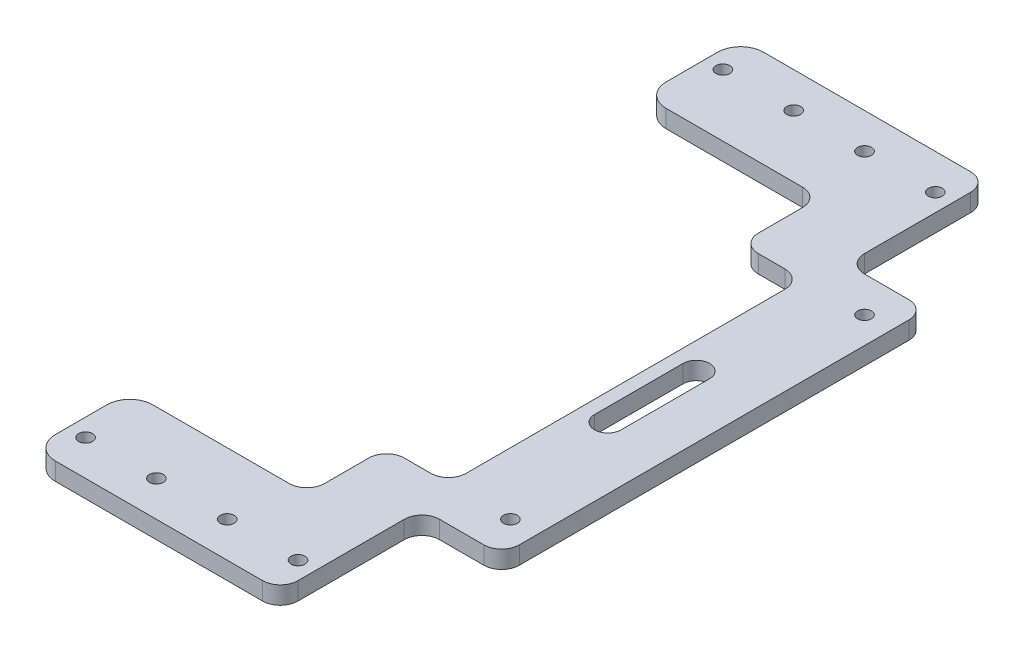
SolidWorks part; units mm, degrees
material "PC High Viscosity"
ref_plane "Front Plane" through (0, 0, 0) normal (0, 0, 1) x (1, 0, 0)
ref_plane "Top Plane" through (0, 0, 0) normal (0, 1, 0) x (1, 0, 0)
ref_plane "Right Plane" through (0, 0, 0) normal (1, 0, 0) x (0, 0, -1)
sketch "Sketch1" plane through (0, 0, 0) normal (0, 1, 0) x (1, 0, 0)
  line L0 (0, 0) -> (0, 50.8)
  line L5 (0, 50.8) -> (-28.575, 50.8)
  line L6 (-28.575, 50.8) -> (-28.575, 203.2)
  line L7 (-28.575, 203.2) -> (0, 203.2)
  line L8 (0, 203.2) -> (0, 254)
  line L9 (0, 254) -> (215.9, 254)
  line L10 (215.9, 254) -> (215.9, 203.2)
  line L11 (215.9, 203.2) -> (244.475, 203.2)
  line L12 (244.475, 203.2) -> (244.475, 50.8)
  line L13 (244.475, 50.8) -> (215.9, 50.8)
  line L14 (215.9, 50.8) -> (215.9, 0)
  line L15 (215.9, 0) -> (0, 0)
  line L16 (101.6, 219.075) -> (101.6, 34.925) construction
  line L17 (12.7, 219.075) -> (190.5, 219.075)
  line L18 (12.7, 219.075) -> (12.7, 34.925)
  line L19 (12.7, 34.925) -> (190.5, 34.925)
  line L20 (190.5, 219.075) -> (190.5, 34.925)
  line L21 (-9.525, 63.5) -> (12.7, 63.5)
  line L22 (-9.525, 63.5) -> (-9.525, 190.5)
  line L23 (-9.525, 190.5) -> (12.7, 190.5)
  line L24 (12.7, 63.5) -> (12.7, 190.5)
  line L25 (212.725, 190.5) -> (190.5, 190.5)
  line L26 (190.5, 63.5) -> (190.5, 190.5)
  line L27 (212.725, 63.5) -> (190.5, 63.5)
  line L28 (212.725, 63.5) -> (212.725, 190.5)
  line L29 (12.7, 127) -> (-9.525, 127) construction
  line L30 (-19.05, 111.125) -> (-19.05, 142.875) construction
  line L31 (-23.8125, 111.125) -> (-23.8125, 142.875)
  line L32 (-14.2875, 111.125) -> (-14.2875, 142.875)
  line L33 (222.25, 111.125) -> (222.25, 142.875) construction
  line L34 (227.0125, 111.125) -> (227.0125, 142.875)
  line L35 (217.4875, 111.125) -> (217.4875, 142.875)
  line L36 (12.7, 219.075) -> (12.7, 254) construction
  line L37 (12.7, 34.925) -> (12.7, 0) construction
  circle A0 centre (209.55, 241.3) radius 2.4892
  circle A1 centre (209.55, 12.7) radius 2.4892
  arc A2 (-23.8125, 111.125) -> (-14.2875, 111.125) centre (-19.05, 111.125) ccw
  arc A3 (-14.2875, 142.875) -> (-23.8125, 142.875) centre (-19.05, 142.875) ccw
  arc A4 (227.0125, 111.125) -> (217.4875, 111.125) centre (222.25, 111.125) cw
  arc A5 (217.4875, 142.875) -> (227.0125, 142.875) centre (222.25, 142.875) cw
  point P34 (-19.05, 127)
  point P44 (222.25, 127)
  dimension "D10" = 4.9784
  dimension "D1" = 177.8
  dimension "D5" = 12.7
  dimension "D6" = 25.4
  dimension "D7" = 152.4
  dimension "D8" = 22.225
  dimension "D9" = 19.05
  dimension "D11" = 12.7
  dimension "D12" = 12.7
  dimension "D13" = 6.35
  dimension "D14" = 12.7
  dimension "D15" = 9.525
  dimension "D16" = 9.525
  dimension "D17" = 31.75
  dimension "D2" = 254
  dimension "D3" = 184.15
extrude "Boss-Extrude1" add sketch "Sketch1" along normal mid plane 6.35 contours L15 L14 L13 L12 L11 L10 L9 L8 L7 L6 L5 L0 A1 A0 L28 L27 L20 L19 L18 L21 L22 L23 L17 L25 region at (3.7292, 0, -25.4)
fillet "Fillet1" radius 6.35 24 edges at (0, 0, 0) (0, 0, -50.8) (-28.575, 0, -50.8) (-28.575, 0, -203.2) (0, 0, -203.2) (0, 0, -254) (215.9, 0, -254) (215.9, 0, -203.2) (244.475, 0, -203.2) (244.475, 0, -50.8) (215.9, 0, -50.8) (215.9, 0, 0) (212.725, 0, -190.5) (190.5, 0, -190.5) (190.5, 0, -219.075) (12.7, 0, -219.075) (-9.525, 0, -190.5) (-9.525, 0, -63.5) (12.7, 0, -63.5) (12.7, 0, -34.925) (190.5, 0, -34.925) (190.5, 0, -63.5) (212.725, 0, -63.5) (12.7, 0, -190.5)
pattern_linear "LPattern1" count 8 spacing 25.4 along (-1, 0, 0) of face at (209.55, 3.175, -238.8108) of face at (209.55, 3.175, -10.2108)
sketch "Sketch2" plane through (0, 3.175, 0) normal (0, 1, 0) x (1, 0, 0)
  line L0 (6.35, 254) -> (209.55, 254) construction
  line L1 (127, 254) -> (-28.575, 254)
  line L2 (127, 254) -> (127, 0)
  line L3 (127, 0) -> (-28.575, 0)
  line L4 (-28.575, 254) -> (-28.575, 0)
  line L5 (209.55, 0) -> (6.35, 0) construction
  line L6 (-28.575, 57.15) -> (-28.575, 196.85) construction
  line L7 (234.95, 190.5) -> (234.95, 63.5) construction
  line L8 (244.475, 196.85) -> (244.475, 57.15) construction
  line L9 (217.4875, 111.125) -> (217.4875, 142.875) construction
  line L10 (222.25, 203.2) -> (238.125, 203.2) construction
  circle A1 centre (184.15, 241.3) radius 2.4892 construction
  circle A2 centre (234.95, 190.5) radius 2.4892
  circle A3 centre (234.95, 63.5) radius 2.4892
  point P16 (234.95, 127)
  point P17 (217.4875, 127)
  dimension "D1" = 57.15
  dimension "D2" = 4.9784
  dimension "D3" = 12.7
  dimension "D4" = 9.525
extrude "Cut-Extrude1" cut sketch "Sketch2" against normal through all
fillet "Fillet2" radius 8.255 4 edges at (127, 0, -219.075) (127, 0, -254) (127, 0, 0) (127, 0, -34.925)
equation "\"D14@Sketch1\"=\"D5@Sketch1\""
